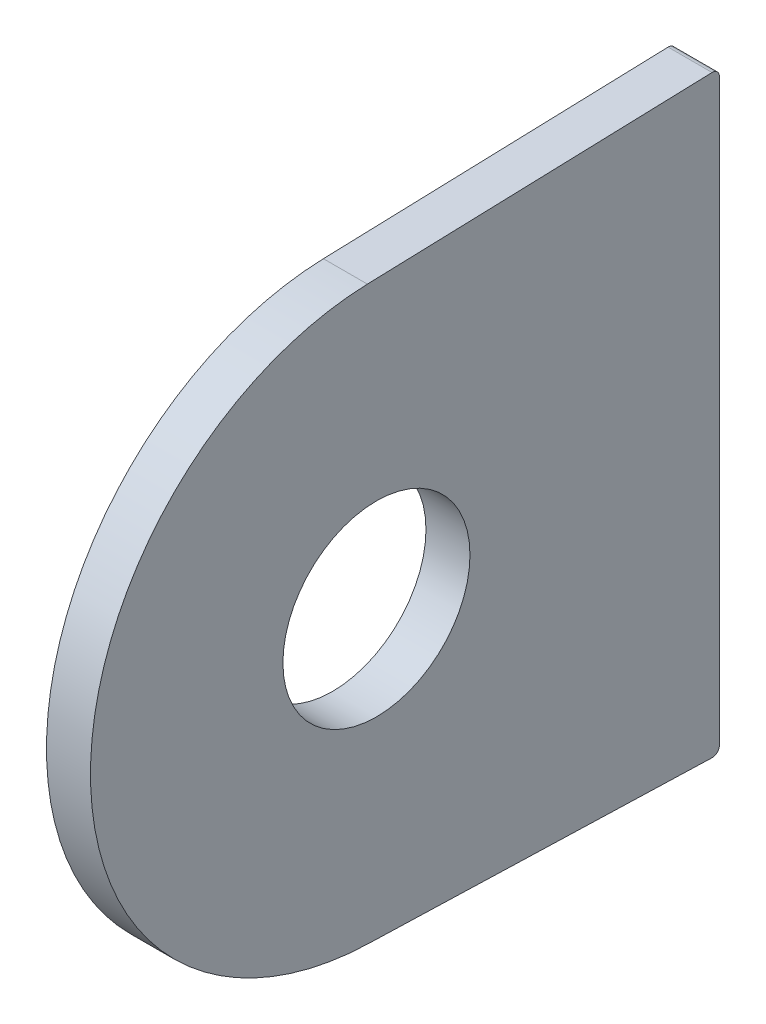
SolidWorks part; units mm, degrees
material "ASTM A36 Steel"
ref_plane "X-Y Datum" through (0, 0, 0) normal (0, 0, 1) x (1, 0, 0)
ref_plane "X-Z Datum" through (0, 0, 0) normal (0, 1, 0) x (1, 0, 0)
ref_plane "Y-Z Datum" through (0, 0, 0) normal (1, 0, 0) x (0, 0, -1)
sketch "Sketch1" plane through (0, 0, 0) normal (1, 0, 0) x (0, 0, -1)
  line L0 (24.747, -21.4312) -> (-0.653, -20.6272)
  line L1 (24.747, 21.4312) -> (-0.653, 20.6272)
  line L2 (24.747, -21.4312) -> (24.747, 21.4312)
  line L3 (6.75, 0) -> (24.747, 0) construction
  arc A0 (-0.653, 20.6272) -> (-0.653, -20.6272) centre (0, 0) ccw
  circle A1 centre (0, 0) radius 6.75
  point P9 (0, 0)
  point P10 (0, 0)
  dimension "D1" = 41.275
  dimension "D2" = 13.5
  dimension "D3" = 42.8625
  dimension "D5" = 13.8875
  dimension "D4" = 25.4
extrude "Boss-Extrude1" add sketch "Sketch1" along normal mid plane 3.175 contours A1 | L0 L2 L1 A0 A1 region at (0, -20.4053, -12.0668) region at (0, 0, 0)
fillet "Fillet1" radius 0.508 1 edges at (0, -21.4313, -24.747)
fillet "Fillet2" radius 0.508 1 edges at (0, 21.4313, -24.747)
hole_wizard "M12 Clearance Hole1" positions "Sketch4" profile "Sketch5" hole size "M12" standard "ANSI Metric" end condition through all
sketch "Sketch4" plane through (-1.5875, 0, 0) normal (-1, 0, 0) x (0, 0, 1)
  point P0 (0, 0)
sketch "Sketch5" plane through (-1.5875, 0, 0) normal (0, 1, 0) x (0, 0, 1)
  line L0 (0, 0) -> (0, 3.175)
  line L1 (0, 3.175) -> (6.75, 3.175)
  line L2 (6.75, 3.175) -> (6.75, 0)
  line L5 (6.75, 0) -> (0, 0)
  line L11 (0, -6.35) -> (0, 107.95) construction
  dimension "Thru Hole Dia." = 13.5
  dimension "Thru Hole Depth" = 3.175
